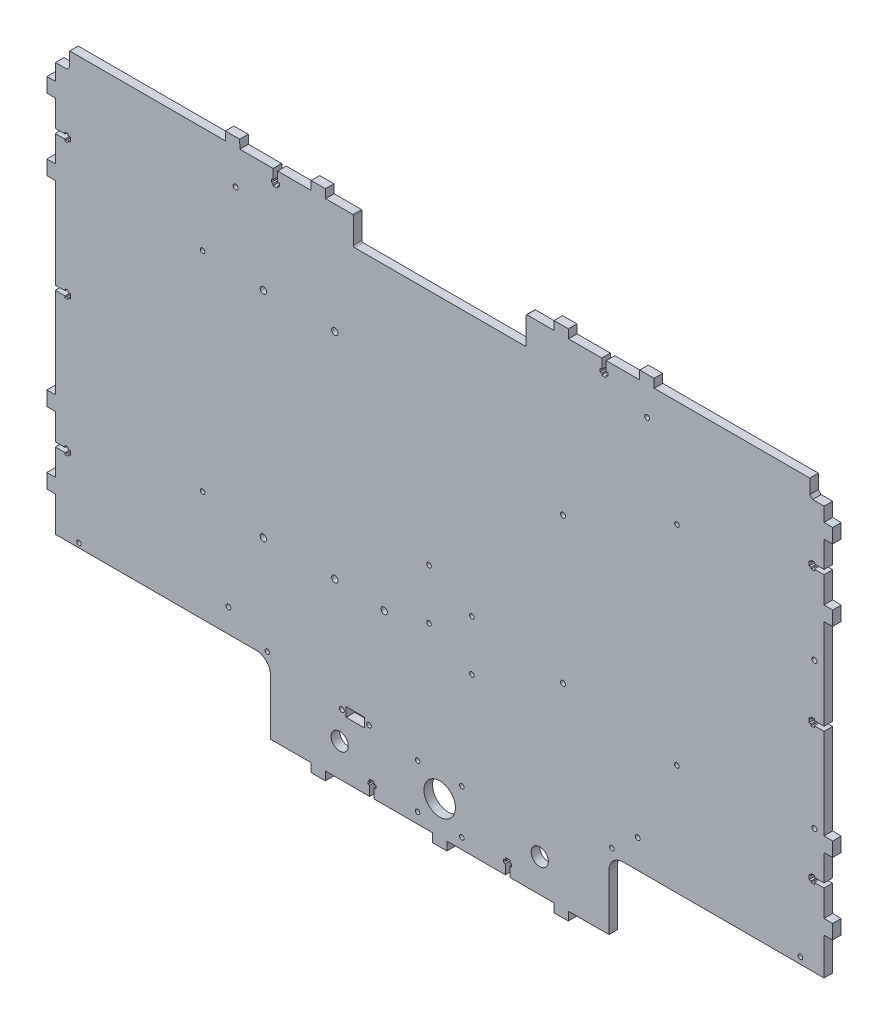
SolidWorks part; units mm, degrees
material "Клен"
ref_plane "Front" through (0, 0, 0) normal (0, 0, 1) x (1, 0, 0)
ref_plane "Top" through (0, 0, 0) normal (0, 1, 0) x (1, 0, 0)
ref_plane "Right" through (0, 0, 0) normal (1, 0, 0) x (0, 0, -1)
sketch "Эскиз1" plane through (0, 0, 0) normal (0, 0, 1) x (1, 0, 0)
  line L0 (89.7419, 500.1376) -> (118.0919, 500.1376)
  line L1 (118.0919, 500.1376) -> (118.1919, 494.1376)
  line L2 (118.1919, 494.1376) -> (128.1919, 494.1376)
  line L3 (128.1919, 494.1376) -> (128.2919, 500.1376)
  line L4 (128.2919, 500.1376) -> (159.1419, 500.1376)
  line L5 (159.1419, 500.1376) -> (159.1419, 506.9376)
  line L6 (159.1419, 506.9376) -> (157.9419, 506.9376)
  line L7 (157.9419, 506.9376) -> (157.9419, 509.1376)
  line L8 (157.9419, 509.1376) -> (159.1419, 509.1376)
  line L9 (159.1419, 509.1376) -> (159.1419, 510.6376)
  line L10 (159.1419, 510.6376) -> (162.2419, 510.6376)
  line L11 (162.2419, 510.6376) -> (162.2419, 509.1376)
  line L12 (162.2419, 509.1376) -> (163.4419, 509.1376)
  line L13 (163.4419, 509.1376) -> (163.4419, 506.9376)
  line L14 (163.4419, 506.9376) -> (162.2419, 506.9376)
  line L15 (162.2419, 506.9376) -> (162.2419, 500.1376)
  line L16 (-51.8081, 695.792) -> (-54.0081, 695.792)
  line L17 (-66.8081, 623.542) -> (-60.8081, 623.442)
  line L18 (162.2419, 500.1376) -> (203.0919, 500.1376)
  line L19 (203.0919, 500.1376) -> (203.1919, 494.1376)
  line L20 (203.1919, 494.1376) -> (213.1919, 494.1376)
  line L21 (213.1919, 494.1376) -> (213.2919, 500.1376)
  line L22 (213.2919, 500.1376) -> (254.1419, 500.1376)
  line L23 (254.1419, 500.1376) -> (254.1419, 506.9376)
  line L24 (254.1419, 506.9376) -> (252.9419, 506.9376)
  line L25 (252.9419, 506.9376) -> (252.9419, 509.1376)
  line L26 (252.9419, 509.1376) -> (254.1419, 509.1376)
  line L27 (254.1419, 509.1376) -> (254.1419, 510.6376)
  line L28 (254.1419, 510.6376) -> (257.2419, 510.6376)
  line L29 (257.2419, 510.6376) -> (257.2419, 509.1376)
  line L30 (257.2419, 509.1376) -> (258.4419, 509.1376)
  line L31 (258.4419, 509.1376) -> (258.4419, 506.9376)
  line L32 (258.4419, 506.9376) -> (257.2419, 506.9376)
  line L33 (257.2419, 506.9376) -> (257.2419, 500.1376)
  line L34 (257.2419, 500.1376) -> (288.0919, 500.1376)
  line L35 (288.0919, 500.1376) -> (288.1919, 494.1376)
  line L36 (288.1919, 494.1376) -> (298.1919, 494.1376)
  line L37 (298.1919, 494.1376) -> (298.2919, 500.1376)
  line L38 (298.2919, 500.1376) -> (326.6419, 500.1376)
  line L97 (367.1919, 847.1376) -> (358.2919, 847.1376)
  line L98 (358.2919, 847.1376) -> (358.1919, 853.1376)
  line L99 (358.1919, 853.1376) -> (348.1919, 853.1376)
  line L100 (348.1919, 853.1376) -> (348.0919, 847.1376)
  line L101 (348.0919, 847.1376) -> (324.7419, 847.1376)
  line L102 (324.7419, 847.1376) -> (324.7419, 840.3376)
  line L103 (324.7419, 840.3376) -> (325.9419, 840.3376)
  line L104 (325.9419, 840.3376) -> (325.9419, 838.1376)
  line L105 (325.9419, 838.1376) -> (324.7419, 838.1376)
  line L106 (324.7419, 838.1376) -> (324.7419, 836.6376)
  line L107 (324.7419, 836.6376) -> (321.6419, 836.6376)
  line L108 (321.6419, 836.6376) -> (321.6419, 838.1376)
  line L109 (321.6419, 838.1376) -> (320.4419, 838.1376)
  line L110 (320.4419, 838.1376) -> (320.4419, 840.3376)
  line L111 (320.4419, 840.3376) -> (321.6419, 840.3376)
  line L112 (321.6419, 840.3376) -> (321.6419, 847.1376)
  line L113 (321.6419, 847.1376) -> (298.2919, 847.1376)
  line L114 (298.2919, 847.1376) -> (298.1919, 853.1376)
  line L115 (298.1919, 853.1376) -> (288.1919, 853.1376)
  line L116 (288.1919, 853.1376) -> (288.0919, 847.1376)
  line L117 (288.0919, 847.1376) -> (269.1919, 847.1376)
  line L118 (268.6919, 846.6376) -> (268.6919, 828.542)
  line L119 (267.6919, 827.542) -> (148.6919, 827.542)
  line L120 (147.6919, 828.542) -> (147.6919, 846.542)
  line L121 (147.1919, 847.042) -> (128.2919, 847.042)
  line L122 (128.2919, 847.042) -> (128.1919, 853.042)
  line L123 (128.1919, 853.042) -> (118.1919, 853.042)
  line L124 (118.1919, 853.042) -> (118.0919, 847.042)
  line L125 (118.0919, 847.042) -> (94.7419, 847.042)
  line L126 (94.7419, 847.042) -> (94.7419, 840.242)
  line L127 (94.7419, 840.242) -> (95.9419, 840.242)
  line L128 (95.9419, 840.242) -> (95.9419, 838.042)
  line L129 (95.9419, 838.042) -> (94.7419, 838.042)
  line L130 (94.7419, 838.042) -> (94.7419, 836.542)
  line L131 (94.7419, 836.542) -> (91.6419, 836.542)
  line L132 (91.6419, 836.542) -> (91.6419, 838.042)
  line L133 (91.6419, 838.042) -> (90.4419, 838.042)
  line L134 (90.4419, 838.042) -> (90.4419, 840.242)
  line L135 (90.4419, 840.242) -> (91.6419, 840.242)
  line L136 (91.6419, 840.242) -> (91.6419, 847.042)
  line L137 (91.6419, 847.042) -> (68.2919, 847.042)
  line L138 (68.2919, 847.042) -> (68.1919, 853.042)
  line L139 (68.1919, 853.042) -> (58.1919, 853.042)
  line L140 (58.1919, 853.042) -> (58.0919, 847.042)
  line L141 (58.0919, 847.042) -> (49.1919, 847.042)
  line L199 (39.1919, 871.432) -> (39.1919, 501.6876) construction
  line L201 (142.7002, 546.3976) -> (155.7002, 546.3976)
  line L202 (155.7002, 546.3976) -> (155.7002, 539.8976)
  line L203 (155.7002, 539.8976) -> (142.7002, 539.8976)
  line L204 (142.7002, 539.8976) -> (142.7002, 546.3976)
  line L205 (-60.8081, 871.432) -> (-60.8081, 501.6876) construction
  line L206 (-50.3081, 791.992) -> (-51.8081, 791.992)
  line L207 (-60.8081, 696.992) -> (-60.8081, 633.642)
  line L208 (-60.8081, 795.092) -> (-54.0081, 795.092)
  line L209 (-51.8081, 791.992) -> (-51.8081, 790.792)
  line L210 (-54.0081, 700.092) -> (-54.0081, 701.292)
  line L211 (-51.8081, 700.092) -> (-50.3081, 700.092)
  line L212 (-60.8081, 835.042) -> (-60.8081, 823.642)
  line L213 (-51.8081, 795.092) -> (-50.3081, 795.092)
  line L214 (-54.0081, 701.292) -> (-51.8081, 701.292)
  line L215 (-50.3081, 696.992) -> (-51.8081, 696.992)
  line L216 (-54.0081, 601.992) -> (-60.8081, 601.992)
  line L217 (-60.8081, 773.642) -> (-66.8081, 773.542)
  line L218 (-50.3081, 601.992) -> (-51.8081, 601.992)
  line L219 (-60.8081, 813.442) -> (-60.8081, 795.092)
  line L220 (-54.0081, 795.092) -> (-54.0081, 796.292)
  line L221 (-54.0081, 796.292) -> (-51.8081, 796.292)
  line L222 (-51.8081, 696.992) -> (-51.8081, 695.792)
  line L223 (-54.0081, 606.292) -> (-51.8081, 606.292)
  line L224 (-60.8081, 573.442) -> (-60.8081, 549.042)
  line L225 (-52.8081, 835.042) -> (-60.8081, 835.042)
  line L226 (-54.0081, 790.792) -> (-54.0081, 791.992)
  line L227 (-51.8081, 605.092) -> (-50.3081, 605.092)
  line L228 (-66.8081, 583.542) -> (-66.8081, 573.542)
  line L229 (-51.8081, 790.792) -> (-54.0081, 790.792)
  line L230 (-54.0081, 605.092) -> (-54.0081, 606.292)
  line L231 (-51.8081, 601.992) -> (-51.8081, 600.792)
  line L232 (-66.8081, 823.542) -> (-66.8081, 813.542)
  line L233 (-50.3081, 795.092) -> (-50.3081, 791.992)
  line L234 (-60.8081, 633.642) -> (-66.8081, 633.542)
  line L235 (-60.8081, 583.642) -> (-66.8081, 583.542)
  line L236 (-66.8081, 813.542) -> (-60.8081, 813.442)
  line L237 (-66.8081, 773.542) -> (-66.8081, 763.542)
  line L238 (-51.8081, 600.792) -> (-54.0081, 600.792)
  line L239 (-66.8081, 763.542) -> (-60.8081, 763.442)
  line L240 (-50.3081, 700.092) -> (-50.3081, 696.992)
  line L241 (-60.8081, 623.442) -> (-60.8081, 605.092)
  line L243 (-54.0081, 791.992) -> (-60.8081, 791.992)
  line L244 (-54.0081, 695.792) -> (-54.0081, 696.992)
  line L245 (-60.8081, 823.642) -> (-66.8081, 823.542)
  line L246 (-51.8081, 796.292) -> (-51.8081, 795.092)
  line L247 (-51.8081, 701.292) -> (-51.8081, 700.092)
  line L248 (-60.8081, 601.992) -> (-60.8081, 583.642)
  line L249 (-54.0081, 696.992) -> (-60.8081, 696.992)
  line L250 (-66.8081, 633.542) -> (-66.8081, 623.542)
  line L251 (-60.8081, 763.442) -> (-60.8081, 700.092)
  line L252 (-54.0081, 600.792) -> (-54.0081, 601.992)
  line L254 (-50.8081, 847.042) -> (-50.8081, 837.042)
  line L255 (-50.8081, 837.042) -> (-52.8081, 835.042)
  line L256 (-60.8081, 700.092) -> (-54.0081, 700.092)
  line L257 (-60.8081, 605.092) -> (-54.0081, 605.092)
  line L258 (-50.3081, 605.092) -> (-50.3081, 601.992)
  line L259 (-60.8081, 791.992) -> (-60.8081, 773.642)
  line L260 (-51.8081, 606.292) -> (-51.8081, 605.092)
  line L261 (-66.8081, 573.542) -> (-60.8081, 573.442)
  line L263 (-50.8081, 847.042) -> (49.1919, 847.042)
  line L264 (377.1919, 871.432) -> (377.1919, 476.2445) construction
  line L265 (477.1919, 871.432) -> (477.1919, 476.2445) construction
  line L266 (477.1919, 625.0876) -> (483.1919, 625.1876)
  line L267 (466.6919, 698.6376) -> (466.6919, 701.7376)
  line L268 (477.1919, 549.1376) -> (477.1919, 575.0876)
  line L269 (470.3919, 701.7376) -> (477.1919, 701.7376)
  line L270 (477.1919, 585.2876) -> (477.1919, 603.6376)
  line L271 (477.1919, 796.7376) -> (477.1919, 815.0876)
  line L272 (477.1919, 575.0876) -> (483.1919, 575.1876)
  line L273 (468.1919, 603.6376) -> (466.6919, 603.6376)
  line L274 (477.1919, 635.2876) -> (477.1919, 698.6376)
  line L275 (470.3919, 792.4376) -> (468.1919, 792.4376)
  line L276 (467.1919, 837.1376) -> (467.1919, 847.1376)
  line L277 (483.1919, 635.1876) -> (477.1919, 635.2876)
  line L278 (468.1919, 796.7376) -> (468.1919, 797.9376)
  line L279 (483.1919, 585.1876) -> (477.1919, 585.2876)
  line L280 (468.1919, 698.6376) -> (466.6919, 698.6376)
  line L281 (468.1919, 793.6376) -> (466.6919, 793.6376)
  line L282 (469.1919, 835.1376) -> (467.1919, 837.1376)
  line L283 (483.1919, 575.1876) -> (483.1919, 585.1876)
  line L284 (470.3919, 603.6376) -> (470.3919, 602.4376)
  line L285 (470.3919, 697.4376) -> (468.1919, 697.4376)
  line L286 (477.1919, 701.7376) -> (477.1919, 765.0876)
  line L287 (477.1919, 793.6376) -> (470.3919, 793.6376)
  line L288 (483.1919, 815.1876) -> (483.1919, 825.1876)
  line L289 (470.3919, 606.7376) -> (477.1919, 606.7376)
  line L290 (470.3919, 698.6376) -> (470.3919, 697.4376)
  line L291 (483.1919, 775.1876) -> (477.1919, 775.2876)
  line L292 (466.6919, 603.6376) -> (466.6919, 606.7376)
  line L293 (466.6919, 793.6376) -> (466.6919, 796.7376)
  line L294 (470.3919, 797.9376) -> (470.3919, 796.7376)
  line L295 (477.1919, 825.2876) -> (477.1919, 835.1376)
  line L296 (470.3919, 602.4376) -> (468.1919, 602.4376)
  line L297 (483.1919, 625.1876) -> (483.1919, 635.1876)
  line L298 (468.1919, 697.4376) -> (468.1919, 698.6376)
  line L299 (470.3919, 702.9376) -> (470.3919, 701.7376)
  line L301 (468.1919, 607.9376) -> (470.3919, 607.9376)
  line L302 (470.3919, 793.6376) -> (470.3919, 792.4376)
  line L303 (466.6919, 796.7376) -> (468.1919, 796.7376)
  line L304 (477.1919, 603.6376) -> (470.3919, 603.6376)
  line L305 (477.1919, 606.7376) -> (477.1919, 625.0876)
  line L306 (477.1919, 775.2876) -> (477.1919, 793.6376)
  line L307 (468.1919, 792.4376) -> (468.1919, 793.6376)
  line L308 (477.1919, 815.0876) -> (483.1919, 815.1876)
  line L309 (466.6919, 606.7376) -> (468.1919, 606.7376)
  line L310 (468.1919, 606.7376) -> (468.1919, 607.9376)
  line L311 (466.6919, 701.7376) -> (468.1919, 701.7376)
  line L312 (468.1919, 702.9376) -> (470.3919, 702.9376)
  line L313 (468.1919, 797.9376) -> (470.3919, 797.9376)
  line L315 (470.3919, 607.9376) -> (470.3919, 606.7376)
  line L316 (477.1919, 698.6376) -> (470.3919, 698.6376)
  line L317 (468.1919, 701.7376) -> (468.1919, 702.9376)
  line L318 (477.1919, 765.0876) -> (483.1919, 765.1876)
  line L319 (470.3919, 796.7376) -> (477.1919, 796.7376)
  line L320 (468.1919, 602.4376) -> (468.1919, 603.6376)
  line L321 (483.1919, 765.1876) -> (483.1919, 775.1876)
  line L322 (483.1919, 825.1876) -> (477.1919, 825.2876)
  line L323 (477.1919, 835.1376) -> (469.1919, 835.1376)
  line L325 (367.1919, 847.1376) -> (467.1919, 847.1376)
  line L326 (336.6419, 549.1376) -> (377.1919, 549.1376)
  line L327 (326.6419, 500.1376) -> (326.6419, 539.1376)
  line L328 (377.1919, 549.1376) -> (477.1919, 549.1376)
  line L329 (89.7419, 539.042) -> (89.7419, 500.1376)
  line L330 (79.7419, 549.042) -> (39.1919, 549.042)
  line L331 (-60.8081, 549.042) -> (39.1919, 549.042)
  line L332 (208.1919, 486.1481) -> (208.1919, 880.8098) construction
  line L333 (107.749, 552.1376) -> (-66.0548, 552.1376) construction
  line L334 (315.5919, 553.6876) -> (489.3697, 553.6876) construction
  line L335 (87.5419, 557.9345) -> (87.5419, 540.5243) construction
  line L336 (328.7419, 492.2341) -> (328.7419, 562.4741) construction
  line L337 (42.1919, 871.432) -> (42.1919, 565.6434) construction
  line L338 (-84.499, 772.492) -> (54.9834, 772.492) construction
  line L339 (-84.499, 626.492) -> (54.9834, 626.492) construction
  circle A0 centre (138.1919, 523.1376) radius 6
  circle A1 centre (208.1919, 523.1376) radius 11
  circle A2 centre (278.1919, 523.1376) radius 6
  circle A3 centre (192.6919, 538.6376) radius 1.6
  circle A4 centre (223.6919, 538.6376) radius 1.6
  circle A5 centre (158.7002, 543.1376) radius 1.6265
  circle A6 centre (139.7002, 543.1376) radius 1.7
  circle A7 centre (192.6919, 507.6376) radius 1.6
  circle A8 centre (223.6919, 507.6376) radius 1.6
  circle A9 centre (65.2801, 822.6887) radius 1.7
  circle A10 centre (353.3431, 826.9394) radius 1.7
  circle A11 centre (84.7857, 769.7888) radius 2.25
  circle A12 centre (134.7857, 769.7888) radius 2.25
  circle A13 centre (294.4853, 738.3683) radius 1.75
  circle A15 centre (200.7177, 661.1578) radius 1.6
  circle A16 centre (230.7177, 645.1578) radius 1.6
  circle A17 centre (200.7177, 625.8978) radius 1.6
  circle A18 centre (84.7857, 619.7888) radius 2.25
  circle A19 centre (134.7857, 619.7888) radius 2.25
  circle A20 centre (169.2857, 617.7888) radius 2.25
  circle A21 centre (230.7177, 609.8978) radius 1.6
  circle A22 centre (294.4853, 636.3683) radius 1.75
  circle A24 centre (346.7847, 569.0716) radius 1.7
  circle A26 centre (60.3069, 565.6434) radius 1.7
  arc A30 (148.6919, 827.542) -> (147.6919, 828.542) centre (148.6919, 828.542) cw
  arc A31 (268.6919, 828.542) -> (267.6919, 827.542) centre (267.6919, 828.542) cw
  arc A32 (269.1919, 847.1376) -> (268.6919, 846.6376) centre (269.1919, 846.6376) ccw
  arc A33 (147.6919, 846.542) -> (147.1919, 847.042) centre (147.1919, 846.542) ccw
  circle A36 centre (470.4853, 738.3683) radius 1.75
  circle A37 centre (470.4853, 636.3683) radius 1.75
  arc A38 (326.6419, 539.1376) -> (336.6419, 549.1376) centre (336.6419, 539.1376) cw
  arc A39 (89.7419, 539.042) -> (79.7419, 549.042) centre (79.7419, 539.042) ccw
  circle A40 centre (-44.2581, 552.1376) radius 1.6
  circle A41 centre (460.6419, 553.6876) radius 1.6
  circle A46 centre (87.5419, 552.1376) radius 1.6
  circle A47 centre (328.7419, 553.6876) radius 1.6
  circle A48 centre (42.1919, 772.492) radius 1.6
  circle A49 centre (42.1919, 626.492) radius 1.6
  circle A50 centre (374.1919, 626.492) radius 1.6
  circle A51 centre (374.1919, 772.492) radius 1.6
  dimension "D1" = 12
  dimension "D2" = 22
  dimension "D3" = 12
  dimension "D4" = 169
  dimension "D5" = 1
  dimension "D6" = 0.5
  dimension "D10" = 3.2
  dimension "D12" = 3.2
  dimension "D13" = 16.55
  dimension "D14" = 48.35
  dimension "D15" = 3.2
  dimension "D17" = 3.2
  dimension "D21" = 3.2
  dimension "D22" = 3.2
  dimension "D24" = 23
  dimension "D26" = 31
  dimension "D27" = 31
  dimension "D28" = 31
  dimension "D30" = 23
  dimension "D32" = 43
  dimension "D33" = 43
  dimension "D7" = 100
  dimension "D8" = 100
  dimension "D9" = 169
  dimension "D11" = 16.55
  dimension "D16" = 48.45
  dimension "D18" = 3
  dimension "D19" = 74.55
  dimension "D20" = 146
  dimension "D23" = 23
  dimension "D25" = 7.5
  dimension "D29" = 7.5
  dimension "D31" = 39.76
extrude "Бобышка-Вытянуть1" add sketch "Эскиз1" along normal blind 6 contours L0 L1 L2 L3 L4 L5 L6 L7 L8 L9 L10 L11 L12 L13 L14 L15 L18 L19 L20 L21 L22 L23 L24 L25 L26 L27 L28 L29 L30 L31 L32 L33 L34 L35 L36 L37 L38 region at (208.2305, 684.8227, 0)
